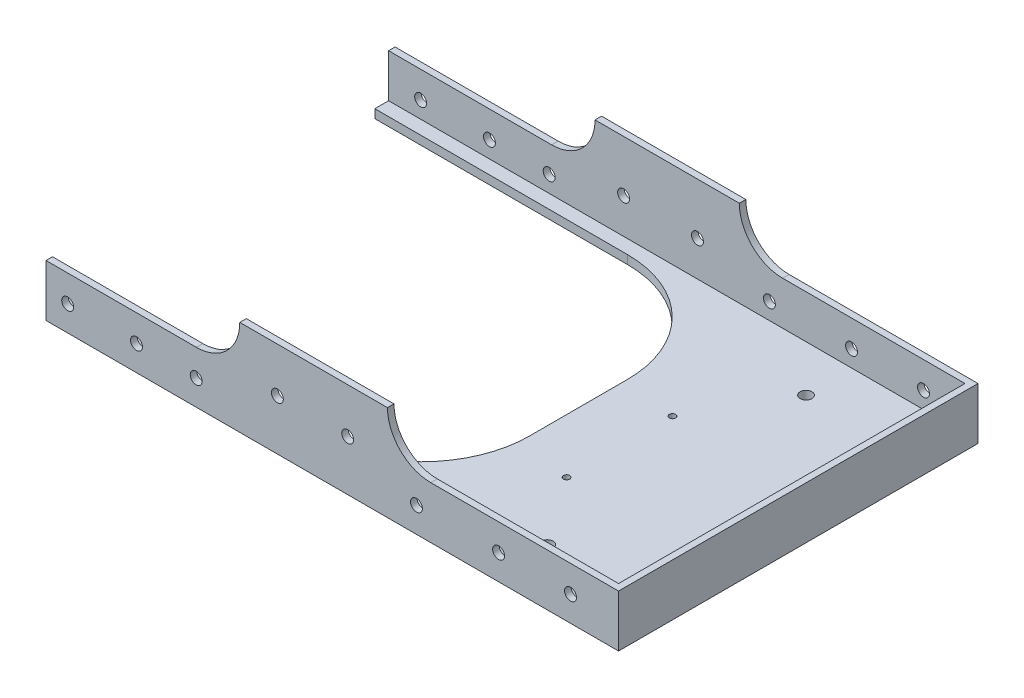
SolidWorks part; units mm, degrees
ref_plane "Front Plane" through (0, 0, 0) normal (0, 0, 1) x (1, 0, 0)
ref_plane "Top Plane" through (0, 0, 0) normal (0, 1, 0) x (1, 0, 0)
ref_plane "Right Plane" through (0, 0, 0) normal (1, 0, 0) x (0, 0, -1)
sketch "Sketch1" plane through (0, 0, 0) normal (0, 1, 0) x (1, 0, 0)
  line L1 (0, 0) -> (278.0499, 0)
  line L2 (0, 0) -> (0, 166.0007)
  line L3 (0, 166.0007) -> (278.0499, 166.0007)
  line L4 (278.0499, 0) -> (278.0499, 166.0007)
extrude "Boss-Extrude1" add sketch "Sketch1" along normal blind 24
sketch "Sketch2" plane through (0, 0, 0) normal (0, -1, 0) x (-1, 0, 0)
  line L1 (-175.4794, 156.6405) -> (14.2402, 156.6405)
  line L2 (-175.4794, 156.6405) -> (-175.4794, 11.5417)
  line L3 (-175.4794, 11.5417) -> (14.2402, 11.5417)
  line L4 (14.2402, 156.6405) -> (14.2402, 11.5417)
extrude "Cut-Extrude1" cut sketch "Sketch2" against normal through all
sketch "Sketch3" plane through (0, 24, 0) normal (0, 1, 0) x (1, 0, 0)
  line L0 (226.9955, 0) -> (226.9955, 3) construction
  line L1 (0, 0) -> (278.0499, 0) construction
  line L2 (278.0499, 166.0007) -> (278.0499, 163.0007) construction
  line L3 (278.0499, 0) -> (278.0499, 166.0007) construction
  line L4 (0, 155.7398) -> (3, 155.7398) construction
  line L5 (0, 166.0007) -> (0, 156.6405) construction
  line L6 (278.0499, 22.4963) -> (275.0499, 22.4963) construction
  line L7 (275.0499, 163.0007) -> (275.0499, 3)
  line L8 (275.0499, 3) -> (3, 3)
  line L9 (3, 3) -> (3, 163.0007)
  line L10 (3, 163.0007) -> (275.0499, 163.0007)
extrude "Cut-Extrude2" cut sketch "Sketch3" against normal blind 20
fillet "Fillet1" radius 50 1 edges at (175.4794, 2, -11.5417) type face fillet first side face at (59.4931, 9.3333, -11.5417) second side face at (175.4794, 2, -84.0911)
fillet "Fillet2" radius 50 1 edges at (175.4794, 2, -156.6405) type face fillet first side face at (175.4794, 2, -109.0911) second side face at (59.4931, 9.3333, -156.6405)
sketch "Sketch4" plane through (0, 24, 0) normal (0, 1, 0) x (1, 0, 0)
  line L0 (0, 0) -> (278.0499, 0) construction
  line L1 (171.3453, 0) -> (103.1403, 0)
  line L2 (171.3453, 0) -> (171.3453, 3)
  line L3 (171.3453, 3) -> (103.1403, 3)
  line L4 (103.1403, 0) -> (103.1403, 3)
  line L5 (3, 3) -> (275.0499, 3) construction
extrude "Boss-Extrude2" add sketch "Sketch4" along normal blind 20
fillet "Fillet4" radius 20 1 edges at (103.1403, 24, -1.5) type face fillet first side face at (103.1403, 34, -1.5) second side face at (35.3801, 24, -4.8472)
fillet "Fillet5" radius 20 1 edges at (171.3453, 24, -1.5) type face fillet first side face at (145.489, 24, -97.7284) second side face at (171.3453, 34, -1.5)
sketch "Sketch5" plane through (0, 24, 0) normal (0, 1, 0) x (1, 0, 0)
  line L0 (278.0499, 166.0007) -> (0, 166.0007) construction
  line L1 (104.1867, 166.0007) -> (170.8443, 166.0007)
  line L2 (104.1867, 166.0007) -> (104.1867, 163.0007)
  line L3 (104.1867, 163.0007) -> (170.8443, 163.0007)
  line L4 (170.8443, 166.0007) -> (170.8443, 163.0007)
  line L5 (275.0499, 163.0007) -> (3, 163.0007) construction
extrude "Boss-Extrude3" add sketch "Sketch5" along normal blind 20
fillet "Fillet6" radius 20 1 edges at (104.1867, 24, -164.5007) type face fillet first side face at (104.1867, 34, -164.5007) second side face at (35.7289, 24, -161.8806)
fillet "Fillet7" radius 20 1 edges at (170.8443, 24, -164.5007) type face fillet first side face at (170.8443, 34, -164.5007) second side face at (228.8223, 24, -83.0003)
sketch "Sketch6" plane through (0, 0, -163.0007) normal (0, 0, 1) x (1, 0, 0)
  circle A0 centre (151.5064, 20.306) radius 2.75
  circle A1 centre (117.3926, 20.306) radius 2.75
extrude "HolesForBolts1" cut sketch "Sketch6" against normal through all
sketch "Sketch7" plane through (0, 0, -166.0007) normal (0, 0, -1) x (-1, 0, 0)
  circle A0 centre (-23.6542, 11.6758) radius 2.75
  circle A1 centre (-55.4415, 11.6758) radius 2.75
  circle A2 centre (-83.0044, 11.6758) radius 2.75
  circle A3 centre (-184.7276, 11.6758) radius 2.75
  circle A4 centre (-222.6455, 11.6758) radius 2.75
  circle A5 centre (-255.8817, 11.6758) radius 2.75
extrude "Cut-Extrude4" cut sketch "Sketch7" against normal through all
sketch "Sketch8" plane through (0, 0, -3) normal (0, 0, -1) x (-1, 0, 0)
  circle A0 centre (-120.4871, 23.2804) radius 2.75
  circle A1 centre (-152.9663, 23.2804) radius 2.75
extrude "Cut-Extrude5" cut sketch "Sketch8" against normal blind 20
ref_plane "Plane1" through (0, 0, -11.5417) normal (0, 0, 1) x (1, 0, 0)
sketch "Sketch11" plane through (0, 0, 0) normal (0, -1, 0) x (1, 0, 0)
  line L0 (125.4794, -11.5417) -> (0, -11.5417) construction
  line L1 (0, 0) -> (13.6461, 0)
  line L2 (0, 0) -> (0, -11.5417)
  line L3 (0, -11.5417) -> (13.6461, -11.5417)
  line L4 (13.6461, 0) -> (13.6461, -11.5417)
extrude "Cut-Extrude6" cut sketch "Sketch11" against normal through all
sketch "Sketch12" plane through (0, 0, 0) normal (0, -1, 0) x (1, 0, 0)
  line L0 (0, -156.6405) -> (125.4794, -156.6405) construction
  line L1 (0, -166.0007) -> (8.8441, -166.0007)
  line L2 (0, -166.0007) -> (0, -156.6405)
  line L3 (0, -156.6405) -> (8.8441, -156.6405)
  line L4 (8.8441, -166.0007) -> (8.8441, -156.6405)
extrude "Cut-Extrude7" cut sketch "Sketch12" against normal through all
sketch "HolesInLidForPiCover" plane through (0, 0, 0) normal (0, -1, 0) x (1, 0, 0)
  circle A0 centre (223.0138, -141.6086) radius 2.75
  circle A1 centre (223.0138, -22.1297) radius 2.75
extrude "Cut-Extrude8" cut sketch "HolesInLidForPiCover" against normal up to surface (4 mm away) up to face at (121.7709, 4, -83.6548)
ref_point "RasPiBoltPoint1"
ref_point "RasPiBoltPoint2"
ref_point "RasPiBoltPoint3"
ref_point "RasPiBoltPoint4"
sketch "LidHolesForPi" plane through (0, 0, 0) normal (0, -1, 0) x (1, 0, 0)
  circle A0 centre (200.5621, -102.3707) radius 1.455
  circle A1 centre (200.5621, -53.5029) radius 1.455
  circle A2 centre (258.5449, -53.5029) radius 1.455
  circle A3 centre (258.5449, -102.3707) radius 1.455
extrude "Cut-Extrude9" cut sketch "LidHolesForPi" against normal up to surface (4 mm away) up to face at (223.0138, 4, -24.8797)
ref_point "LidHoleForCoverLocation1"
ref_point "LidHoleForCoverLocation2"
sketch "Sketch14" plane through (0, 0, 0) normal (0, -1, 0) x (1, 0, 0)
  circle A0 centre (264.7636, -18.9201) radius 2.75
  circle A1 centre (181.6168, -18.9187) radius 2.75
extrude "Cut-Extrude10" cut sketch "Sketch14" against normal up to surface (4 mm away) up to face at (258.5449, 4, -54.9579)
